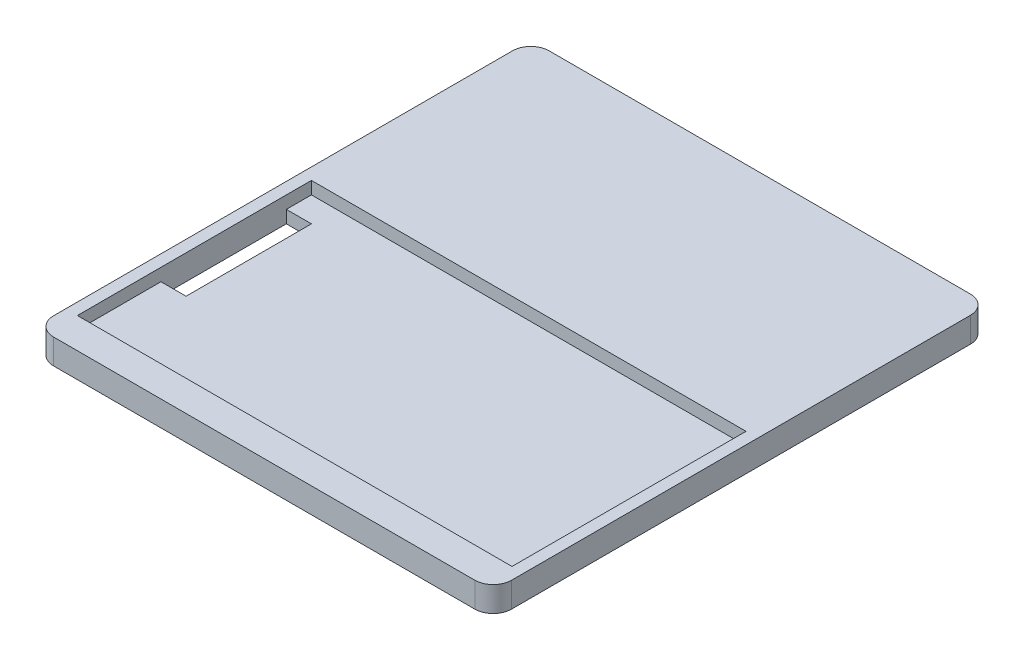
SolidWorks part; units mm, degrees
ref_plane "Front Plane" through (0, 0, 0) normal (0, 0, 1) x (1, 0, 0)
ref_plane "Top Plane" through (0, 0, 0) normal (0, 1, 0) x (1, 0, 0)
ref_plane "Right Plane" through (0, 0, 0) normal (1, 0, 0) x (0, 0, -1)
sketch "Sketch1" plane through (0, 0, 0) normal (0, 1, 0) x (1, 0, 0)
  line L1 (-27.4, -29.65) -> (27.4, -29.65)
  line L2 (-27.4, -29.65) -> (-27.4, 29.65)
  line L3 (-27.4, 29.65) -> (27.4, 29.65)
  line L4 (27.4, -29.65) -> (27.4, 29.65)
  line L5 (-27.4, -29.65) -> (27.4, 29.65) construction
  line L6 (-27.4, 29.65) -> (27.4, -29.65) construction
  point P0 (0, 0)
  dimension "D1" = 54.8
  dimension "D2" = 59.3
extrude "Boss-Extrude1" add sketch "Sketch1" along normal blind 3
fillet "Fillet1" radius 2.2 4 edges at (27.4, 1.5, 29.65) (-27.4, 1.5, 29.65) (-27.4, 1.5, -29.65) (27.4, 1.5, -29.65)
sketch "Sketch2" plane through (0, 3, 0) normal (0, 1, 0) x (1, 0, 0)
  line L0 (0, 20.8073) -> (0, -24.5187) construction
  line L1 (-21.4785, 0) -> (24.4792, 0) construction
  line L3 (-26, -26) -> (26, -26)
  line L4 (-26, -26) -> (-26, 2)
  line L5 (-26, 2) -> (26, 2)
  line L6 (26, -26) -> (26, 2)
  line L7 (-26, -26) -> (26, 2) construction
  line L8 (-26, 2) -> (26, -26) construction
  line L9 (-26, -1) -> (-23, -1)
  line L10 (-26, -1) -> (-26, -16)
  line L11 (-26, -16) -> (-23, -16)
  line L12 (-23, -1) -> (-23, -16)
  point P5 (0, -12)
  point P14 (0, 0)
  dimension "D1" = 52
  dimension "D2" = 28
  dimension "D3" = 3
  dimension "D4" = 15
  dimension "D5" = 3
  dimension "D6" = 12
extrude "Cut-Extrude1" cut sketch "Sketch2" against normal through all contours L12 L9 L4 L11 region at (-24.5, 3, 8.5)
extrude "Cut-Extrude2" cut sketch "Sketch2<3>" against normal blind 1.5 contours L9 L12 L11 L4 L3 L6 L5 region at (0.7814, 3, 12.1116)
sketch "Sketch2<3>" plane through (0, 3, 0) normal (0, 1, 0) x (1, 0, 0) same geometry as "Sketch2"
